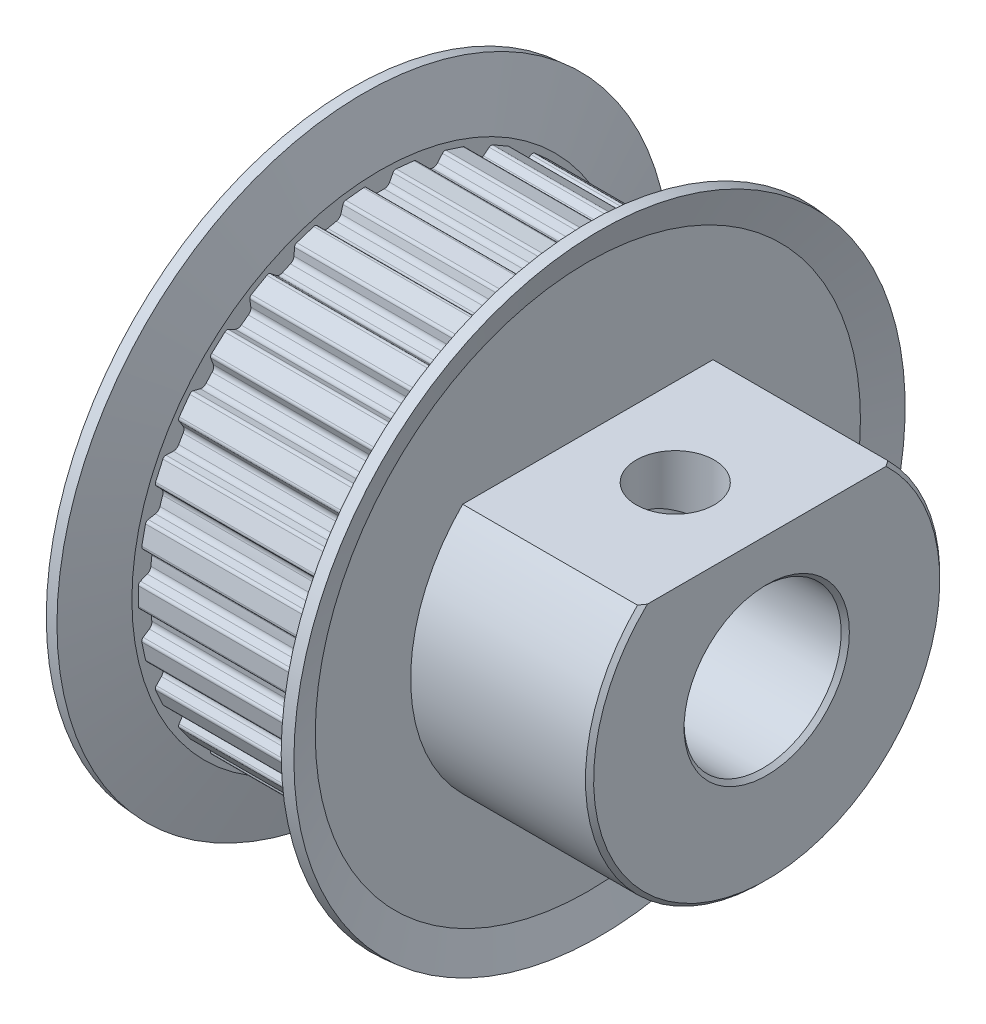
SolidWorks part; units mm, degrees
ref_plane "Front Plane" through (0, 0, 0) normal (0, 0, 1) x (1, 0, 0)
ref_plane "Top Plane" through (0, 0, 0) normal (0, 1, 0) x (1, 0, 0)
ref_plane "Right Plane" through (0, 0, 0) normal (1, 0, 0) x (0, 0, -1)
ref_plane "Plane1" through (0, 0, 0) normal (0, 0, -1) x (-1, 0, 0)
sketch "Sketch1" plane through (0, 0, 0) normal (0, 0, -1) x (-1, 0, 0)
  line L0 (-0.6794, 10.668) -> (-0.6794, 0)
  line L1 (-0.6794, 0) -> (8.0962, 0)
  line L2 (8.0962, 0) -> (8.0962, 10.668)
  line L3 (8.0962, 10.668) -> (8.5534, 11.9615)
  line L4 (8.5534, 11.9615) -> (8.0963, 12.0015)
  line L5 (8.0963, 12.0015) -> (7.4612, 9.7028)
  line L6 (7.4612, 9.7028) -> (7.4612, 8.9916)
  line L7 (7.4612, 8.9916) -> (0.0953, 8.9916)
  line L8 (0.0953, 8.9916) -> (0.0953, 9.7028)
  line L9 (0.0953, 9.7028) -> (-0.6794, 12.0015)
  line L10 (-0.6794, 12.0015) -> (-1.1366, 11.9615)
  line L11 (-1.1366, 11.9615) -> (-0.6794, 10.668)
  line L12 (-1.1366, 0) -> (8.5534, 0) construction
revolve "Revolve1" add sketch "Sketch1" angle 360 about L12 reverse direction yes
sketch "Sketch2" plane through (-8.0962, 0, 0) normal (-1, 0, 0) x (0, 0, 1)
  circle A0 centre (0, 0) radius 6.9342
extrude "Boss-Extrude1" add sketch "Sketch2" along normal blind 0.635
sketch "Sketch3" plane through (0.6794, 0, 0) normal (1, 0, 0) x (0, 0, -1)
  circle A0 centre (0, 0) radius 6.9342
extrude "Boss-Extrude2" add sketch "Sketch3" along normal blind 7
hole_wizard "Hole1" positions "Sketch5" profile "Sketch4" legacy
sketch "Sketch5" plane through (-8.7312, 0, 0) normal (-1, 0, 0) x (0, 0, 1)
  point P0 (0, 0)
sketch "Sketch4" plane through (-8.7312, 0, 0) normal (0, 1, 0) x (0, 0, 1)
  line L0 (0, 0) -> (0, 16.4107)
  line L1 (0, 16.4107) -> (3.075, 16.4107)
  line L2 (3.075, 16.4107) -> (3.075, 0)
  line L3 (3.075, 0) -> (0, 0)
  line L4 (0, 110) -> (0, -10) construction
  dimension "Diameter" = 6.15
  dimension "Depth" = 16.4107
sketch "Sketch8" plane through (0, 0, 0) normal (0, 1, 0) x (1, 0, 0)
  line L0 (-7.4612, -9.4488) -> (-0.0953, -9.4488)
rib "Rib1" sketch "Sketch8" sketch "Sketch8" thickness 0.8682 extrusion direction parallel to sketch draft on yes draft angle 22 parameters "D1"=0.8682, "D3"=22
ref_plane "Plane2" through (0, 0, 0) normal (0, -1, 0) x (1, 0, 0)
sketch "Sketch9" plane through (0, 0, 0) normal (0, -1, 0) x (1, 0, 0)
  line L0 (-7.4612, -9.4488) -> (-0.0953, -9.4488)
rib "Rib2" sketch "Sketch9" sketch "Sketch9" thickness 0.8682 extrusion direction parallel to sketch draft on yes draft angle 22 parameters "D1"=0.8682, "D3"=22
ref_plane "Plane3" through (0, 0, 0) normal (0, 0.1045, 0.9945) x (-1, 0, 0)
sketch "Sketch10" plane through (0, 0, 0) normal (0, 0.1045, 0.9945) x (-1, 0, 0)
  line L0 (7.4612, 9.4488) -> (0.0953, 9.4488)
rib "Rib3" sketch "Sketch10" sketch "Sketch10" thickness 0.8682 extrusion direction parallel to sketch draft on yes draft angle 22 parameters "D1"=0.8682, "D3"=22
ref_plane "Plane4" through (0, 0, 0) normal (0, -0.5, 0.866) x (1, 0, 0)
sketch "Sketch11" plane through (0, 0, 0) normal (0, -0.5, 0.866) x (1, 0, 0)
  line L0 (-7.4612, -9.4488) -> (-0.0953, -9.4488)
rib "Rib4" sketch "Sketch11" sketch "Sketch11" thickness 0.8682 extrusion direction parallel to sketch draft on yes draft angle 22 parameters "D1"=0.8682, "D3"=22
ref_plane "Plane5" through (0, 0, 0) normal (0, 0.9135, -0.4067) x (-1, 0, 0)
sketch "Sketch12" plane through (0, 0, 0) normal (0, 0.9135, -0.4067) x (-1, 0, 0)
  line L0 (7.4612, 9.4488) -> (0.0953, 9.4488)
rib "Rib5" sketch "Sketch12" sketch "Sketch12" thickness 0.8682 extrusion direction parallel to sketch draft on yes draft angle 22 parameters "D1"=0.8682, "D3"=22
ref_plane "Plane6" through (0, 0, 0) normal (0, -0.9135, 0.4067) x (1, 0, 0)
sketch "Sketch13" plane through (0, 0, 0) normal (0, -0.9135, 0.4067) x (1, 0, 0)
  line L0 (-7.4612, -9.4488) -> (-0.0953, -9.4488)
rib "Rib6" sketch "Sketch13" sketch "Sketch13" thickness 0.8682 extrusion direction parallel to sketch draft on yes draft angle 22 parameters "D1"=0.8682, "D3"=22
ref_plane "Plane7" through (0, 0, 0) normal (0, 0.809, 0.5878) x (-1, 0, 0)
sketch "Sketch14" plane through (0, 0, 0) normal (0, 0.809, 0.5878) x (-1, 0, 0)
  line L0 (7.4612, 9.4488) -> (0.0953, 9.4488)
rib "Rib7" sketch "Sketch14" sketch "Sketch14" thickness 0.8682 extrusion direction parallel to sketch draft on yes draft angle 22 parameters "D1"=0.8682, "D3"=22
ref_plane "Plane8" through (0, 0, 0) normal (0, -0.5, -0.866) x (1, 0, 0)
sketch "Sketch15" plane through (0, 0, 0) normal (0, -0.5, -0.866) x (1, 0, 0)
  line L0 (-7.4612, -9.4488) -> (-0.0953, -9.4488)
rib "Rib8" sketch "Sketch15" sketch "Sketch15" thickness 0.8682 extrusion direction parallel to sketch draft on yes draft angle 22 parameters "D1"=0.8682, "D3"=22
ref_plane "Plane9" through (0, 0, 0) normal (0, 0.5, -0.866) x (-1, 0, 0)
sketch "Sketch16" plane through (0, 0, 0) normal (0, 0.5, -0.866) x (-1, 0, 0)
  line L0 (7.4612, 9.4488) -> (0.0953, 9.4488)
rib "Rib9" sketch "Sketch16" sketch "Sketch16" thickness 0.8682 extrusion direction parallel to sketch draft on yes draft angle 22 parameters "D1"=0.8682, "D3"=22
ref_plane "Plane10" through (0, 0, 0) normal (0, -0.809, -0.5878) x (1, 0, 0)
sketch "Sketch17" plane through (0, 0, 0) normal (0, -0.809, -0.5878) x (1, 0, 0)
  line L0 (-7.4612, -9.4488) -> (-0.0953, -9.4488)
rib "Rib10" sketch "Sketch17" sketch "Sketch17" thickness 0.8682 extrusion direction parallel to sketch draft on yes draft angle 22 parameters "D1"=0.8682, "D3"=22
ref_plane "Plane11" through (0, 0, 0) normal (0, -0.9135, -0.4067) x (1, 0, 0)
sketch "Sketch18" plane through (0, 0, 0) normal (0, -0.9135, -0.4067) x (1, 0, 0)
  line L0 (-7.4612, -9.4488) -> (-0.0953, -9.4488)
rib "Rib11" sketch "Sketch18" sketch "Sketch18" thickness 0.8682 extrusion direction parallel to sketch draft on yes draft angle 22 parameters "D1"=0.8682, "D3"=22
ref_plane "Plane12" through (0, 0, 0) normal (0, -0.1045, -0.9945) x (1, 0, 0)
sketch "Sketch19" plane through (0, 0, 0) normal (0, -0.1045, -0.9945) x (1, 0, 0)
  line L0 (-7.4612, -9.4488) -> (-0.0953, -9.4488)
rib "Rib12" sketch "Sketch19" sketch "Sketch19" thickness 0.8682 extrusion direction parallel to sketch draft on yes draft angle 22 parameters "D1"=0.8682, "D3"=22
ref_plane "Plane13" through (0, 0, 0) normal (0, -0.9781, 0.2079) x (1, 0, 0)
sketch "Sketch20" plane through (0, 0, 0) normal (0, -0.9781, 0.2079) x (1, 0, 0)
  line L0 (-7.4612, -9.4488) -> (-0.0953, -9.4488)
rib "Rib13" sketch "Sketch20" sketch "Sketch20" thickness 0.8682 extrusion direction parallel to sketch draft on yes draft angle 22 parameters "D1"=0.8682, "D3"=22
ref_plane "Plane14" through (0, 0, 0) normal (0, 0.9135, 0.4067) x (-1, 0, 0)
sketch "Sketch21" plane through (0, 0, 0) normal (0, 0.9135, 0.4067) x (-1, 0, 0)
  line L0 (7.4612, 9.4488) -> (0.0953, 9.4488)
rib "Rib14" sketch "Sketch21" sketch "Sketch21" thickness 0.8682 extrusion direction parallel to sketch draft on yes draft angle 22 parameters "D1"=0.8682, "D3"=22
ref_plane "Plane15" through (0, 0, 0) normal (0, -0.309, -0.9511) x (1, 0, 0)
sketch "Sketch22" plane through (0, 0, 0) normal (0, -0.309, -0.9511) x (1, 0, 0)
  line L0 (-7.4612, -9.4488) -> (-0.0953, -9.4488)
rib "Rib15" sketch "Sketch22" sketch "Sketch22" thickness 0.8682 extrusion direction parallel to sketch draft on yes draft angle 22 parameters "D1"=0.8682, "D3"=22
ref_plane "Plane16" through (0, 0, 0) normal (0, -0.809, 0.5878) x (1, 0, 0)
sketch "Sketch23" plane through (0, 0, 0) normal (0, -0.809, 0.5878) x (1, 0, 0)
  line L0 (-7.4612, -9.4488) -> (-0.0953, -9.4488)
rib "Rib16" sketch "Sketch23" sketch "Sketch23" thickness 0.8682 extrusion direction parallel to sketch draft on yes draft angle 22 parameters "D1"=0.8682, "D3"=22
ref_plane "Plane17" through (0, 0, 0) normal (0, 0.9781, 0.2079) x (-1, 0, 0)
sketch "Sketch24" plane through (0, 0, 0) normal (0, 0.9781, 0.2079) x (-1, 0, 0)
  line L0 (7.4612, 9.4488) -> (0.0953, 9.4488)
rib "Rib17" sketch "Sketch24" sketch "Sketch24" thickness 0.8682 extrusion direction parallel to sketch draft on yes draft angle 22 parameters "D1"=0.8682, "D3"=22
ref_plane "Plane18" through (0, 0, 0) normal (0, -0.9781, -0.2079) x (1, 0, 0)
sketch "Sketch25" plane through (0, 0, 0) normal (0, -0.9781, -0.2079) x (1, 0, 0)
  line L0 (-7.4612, -9.4488) -> (-0.0953, -9.4488)
rib "Rib18" sketch "Sketch25" sketch "Sketch25" thickness 0.8682 extrusion direction parallel to sketch draft on yes draft angle 22 parameters "D1"=0.8682, "D3"=22
ref_plane "Plane19" through (0, 0, 0) normal (0, 0.5, 0.866) x (-1, 0, 0)
sketch "Sketch26" plane through (0, 0, 0) normal (0, 0.5, 0.866) x (-1, 0, 0)
  line L0 (7.4612, 9.4488) -> (0.0953, 9.4488)
rib "Rib19" sketch "Sketch26" sketch "Sketch26" thickness 0.8682 extrusion direction parallel to sketch draft on yes draft angle 22 parameters "D1"=0.8682, "D3"=22
ref_plane "Plane20" through (0, 0, 0) normal (0, -0.6691, 0.7431) x (1, 0, 0)
sketch "Sketch27" plane through (0, 0, 0) normal (0, -0.6691, 0.7431) x (1, 0, 0)
  line L0 (-7.4612, -9.4488) -> (-0.0953, -9.4488)
rib "Rib20" sketch "Sketch27" sketch "Sketch27" thickness 0.8682 extrusion direction parallel to sketch draft on yes draft angle 22 parameters "D1"=0.8682, "D3"=22
ref_plane "Plane21" through (0, 0, 0) normal (0, 0.9781, -0.2079) x (-1, 0, 0)
sketch "Sketch28" plane through (0, 0, 0) normal (0, 0.9781, -0.2079) x (-1, 0, 0)
  line L0 (7.4612, 9.4488) -> (0.0953, 9.4488)
rib "Rib21" sketch "Sketch28" sketch "Sketch28" thickness 0.8682 extrusion direction parallel to sketch draft on yes draft angle 22 parameters "D1"=0.8682, "D3"=22
ref_plane "Plane22" through (0, 0, 0) normal (0, 0.6691, -0.7431) x (-1, 0, 0)
sketch "Sketch29" plane through (0, 0, 0) normal (0, 0.6691, -0.7431) x (-1, 0, 0)
  line L0 (7.4612, 9.4488) -> (0.0953, 9.4488)
rib "Rib22" sketch "Sketch29" sketch "Sketch29" thickness 0.8682 extrusion direction parallel to sketch draft on yes draft angle 22 parameters "D1"=0.8682, "D3"=22
ref_plane "Plane23" through (0, 0, 0) normal (0, 0.6691, 0.7431) x (-1, 0, 0)
sketch "Sketch30" plane through (0, 0, 0) normal (0, 0.6691, 0.7431) x (-1, 0, 0)
  line L0 (7.4612, 9.4488) -> (0.0953, 9.4488)
rib "Rib23" sketch "Sketch30" sketch "Sketch30" thickness 0.8682 extrusion direction parallel to sketch draft on yes draft angle 22 parameters "D1"=0.8682, "D3"=22
ref_plane "Plane24" through (0, 0, 0) normal (0, -0.6691, -0.7431) x (1, 0, 0)
sketch "Sketch31" plane through (0, 0, 0) normal (0, -0.6691, -0.7431) x (1, 0, 0)
  line L0 (-7.4612, -9.4488) -> (-0.0953, -9.4488)
rib "Rib24" sketch "Sketch31" sketch "Sketch31" thickness 0.8682 extrusion direction parallel to sketch draft on yes draft angle 22 parameters "D1"=0.8682, "D3"=22
ref_plane "Plane25" through (0, 0, 0) normal (0, -0.309, 0.9511) x (1, 0, 0)
sketch "Sketch32" plane through (0, 0, 0) normal (0, -0.309, 0.9511) x (1, 0, 0)
  line L0 (-7.4612, -9.4488) -> (-0.0953, -9.4488)
rib "Rib25" sketch "Sketch32" sketch "Sketch32" thickness 0.8682 extrusion direction parallel to sketch draft on yes draft angle 22 parameters "D1"=0.8682, "D3"=22
ref_plane "Plane26" through (0, 0, 0) normal (0, 0.309, 0.9511) x (-1, 0, 0)
sketch "Sketch33" plane through (0, 0, 0) normal (0, 0.309, 0.9511) x (-1, 0, 0)
  line L0 (7.4612, 9.4488) -> (0.0953, 9.4488)
rib "Rib26" sketch "Sketch33" sketch "Sketch33" thickness 0.8682 extrusion direction parallel to sketch draft on yes draft angle 22 parameters "D1"=0.8682, "D3"=22
ref_plane "Plane27" through (0, 0, 0) normal (0, 0.309, -0.9511) x (-1, 0, 0)
sketch "Sketch34" plane through (0, 0, 0) normal (0, 0.309, -0.9511) x (-1, 0, 0)
  line L0 (7.4612, 9.4488) -> (0.0953, 9.4488)
rib "Rib27" sketch "Sketch34" sketch "Sketch34" thickness 0.8682 extrusion direction parallel to sketch draft on yes draft angle 22 parameters "D1"=0.8682, "D3"=22
ref_plane "Plane28" through (0, 0, 0) normal (0, 0.809, -0.5878) x (-1, 0, 0)
sketch "Sketch35" plane through (0, 0, 0) normal (0, 0.809, -0.5878) x (-1, 0, 0)
  line L0 (7.4612, 9.4488) -> (0.0953, 9.4488)
rib "Rib28" sketch "Sketch35" sketch "Sketch35" thickness 0.8682 extrusion direction parallel to sketch draft on yes draft angle 22 parameters "D1"=0.8682, "D3"=22
ref_plane "Plane29" through (0, 0, 0) normal (0, -0.1045, 0.9945) x (1, 0, 0)
sketch "Sketch36" plane through (0, 0, 0) normal (0, -0.1045, 0.9945) x (1, 0, 0)
  line L0 (-7.4612, -9.4488) -> (-0.0953, -9.4488)
rib "Rib29" sketch "Sketch36" sketch "Sketch36" thickness 0.8682 extrusion direction parallel to sketch draft on yes draft angle 22 parameters "D1"=0.8682, "D3"=22
sketch "Sketch37" plane through (0, 0, 0) normal (0, -0.1045, 0.9945) x (1, 0, 0)
  line L0 (-0.0953, 9.4488) -> (-7.4612, 9.4488)
rib "Rib30" sketch "Sketch37" sketch "Sketch37" thickness 0.8682 extrusion direction parallel to sketch draft on yes draft angle 22 parameters "D1"=0.8682, "D3"=22
chamfer "Chamfer2" distance 0.16 angle 45 3 edges at (7.6795, 0, 3.075) (7.6795, 0, -6.9342) (-8.7312, 0, 3.075)
fillet "Fillet1" radius 0.127 60 edges at (-3.7783, 4.2397, -8.4553) (-3.7783, -8.8522, -3.3327) (-3.7783, -3.4466, -8.8085) (-3.7783, -2.3891, 9.1521) (-3.7783, 5.2027, 7.8994) (-3.7783, -0.4341, 9.4488) (-3.7783, 0.4341, -9.4488) (-3.7783, 0.4341, 9.4488) (-3.7783, -6.7314, -6.6451) (-3.7783, 2.3891, 9.1521) (-3.7783, -9.4424, 0.556) (-3.7783, 4.2397, 8.4553) (-3.7783, 5.9051, -7.3891) (-3.7783, 5.9051, 7.3891) (-3.7783, 2.3891, -9.1521) (-3.7783, 7.3123, 5.9999) (-3.7783, -1.5399, -9.3326) (-3.7783, 8.3999, 4.3485) (-3.7783, -5.2027, -7.8994) (-3.7783, 8.8522, 3.3327) (-3.7783, -7.9659, -5.1003) (-3.7783, 9.1205, 2.507) (-3.7783, -9.3517, -1.4194) (-3.7783, 9.3517, 1.4194) (-3.7783, -9.1205, 2.507) (-3.7783, 1.5399, 9.3326) (-3.7783, -4.2397, 8.4553) (-3.7783, -1.5399, 9.3326) (-3.7783, 5.2027, -7.8994) (-3.7783, -3.4466, 8.8085) (-3.7783, 3.4466, -8.8085) (-3.7783, -5.2027, 7.8994) (-3.7783, 1.5399, -9.3326) (-3.7783, -6.7314, 6.6451) (-3.7783, -0.4341, -9.4488) (-3.7783, -7.9659, 5.1003) (-3.7783, -2.3891, -9.1521) (-3.7783, 9.4424, 0.556) (-3.7783, -4.2397, -8.4553) (-3.7783, 9.4424, -0.556) (-3.7783, -5.9051, -7.3891) (-3.7783, 7.9659, 5.1003) (-3.7783, -7.3123, -5.9999) (-3.7783, 6.7314, 6.6451) (-3.7783, -8.3999, -4.3485) (-3.7783, 9.3517, -1.4194) (-3.7783, -9.1205, -2.507) (-3.7783, 9.1205, -2.507) (-3.7783, -9.4424, -0.556) (-3.7783, 8.8522, -3.3327) (-3.7783, -9.3517, 1.4194) (-3.7783, 8.3999, -4.3485) (-3.7783, -8.8522, 3.3327) (-3.7783, 7.9659, -5.1003) (-3.7783, 3.4466, 8.8085) (-3.7783, 7.3123, -5.9999) (-3.7783, 6.7314, -6.6451) (-3.7783, -7.3123, 5.9999) (-3.7783, -5.9051, 7.3891) (-3.7783, -8.3999, 4.3485) tangent propagation no
fillet "Fillet2" radius 0.2286 60 edges at (-3.7783, -8.7246, -2.1748) (-3.7783, -1.2509, 8.9042) (-3.7783, -7.4541, 5.0284) (-3.7783, -7.4541, -5.0284) (-3.7783, 5.78, 6.8877) (-3.7783, -6.2458, -6.4683) (-3.7783, -8.8549, 1.5618) (-3.7783, -4.7644, -7.6256) (-3.7783, -4.7644, 7.6256) (-3.7783, -3.0749, -8.4495) (-3.7783, 2.4789, 8.6432) (-3.7783, -1.2509, -8.9042) (-3.7783, 8.0818, 3.9412) (-3.7783, 1.2509, -8.9042) (-3.7783, -8.9861, -0.3133) (-3.7783, 3.0749, -8.4495) (-3.7783, -8.3367, 3.3687) (-3.7783, 4.7644, -7.6256) (-3.7783, -6.2458, 6.4683) (-3.7783, 6.2458, -6.4683) (-3.7783, -3.0749, 8.4495) (-3.7783, 7.4541, -5.0284) (-3.7783, 0.6277, 8.9697) (-3.7783, 8.9861, 0.3133) (-3.7783, 4.2217, 7.9389) (-3.7783, 8.9861, -0.3133) (-3.7783, 7.0858, 5.5354) (-3.7783, 8.3367, 3.3687) (-3.7783, -8.3367, -3.3687) (-3.7783, 8.8549, 1.5618) (-3.7783, -8.8549, -1.5618) (-3.7783, 8.8549, -1.5618) (-3.7783, -8.9861, 0.3133) (-3.7783, 8.7246, -2.1748) (-3.7783, -8.7246, 2.1748) (-3.7783, 8.3367, -3.3687) (-3.7783, -8.0818, 3.9412) (-3.7783, 8.0818, -3.9412) (-3.7783, -7.0858, 5.5354) (-3.7783, 7.0858, -5.5354) (-3.7783, -5.78, 6.8877) (-3.7783, 5.78, -6.8877) (-3.7783, -4.2217, 7.9389) (-3.7783, 4.2217, -7.9389) (-3.7783, -2.4789, 8.6432) (-3.7783, 2.4789, -8.6432) (-3.7783, -0.6277, 8.9697) (-3.7783, 0.6277, -8.9697) (-3.7783, 1.2509, 8.9042) (-3.7783, -0.6277, -8.9697) (-3.7783, 3.0749, 8.4495) (-3.7783, -2.4789, -8.6432) (-3.7783, 4.7644, 7.6256) (-3.7783, -4.2217, -7.9389) (-3.7783, 6.2458, 6.4683) (-3.7783, -5.78, -6.8877) (-3.7783, 7.4541, 5.0284) (-3.7783, -7.0858, -5.5354) (-3.7783, -8.0818, -3.9412) (-3.7783, 8.7246, 2.1748) tangent propagation no
sketch "Sketch38" plane through (7.6795, 0, 0) normal (1, 0, 0) x (0, 0, -1)
  line L0 (-4.8987, 4.9078) -> (4.8987, 4.9078)
  line L1 (-4.8987, 4.9078) -> (-4.8987, 7.2729)
  line L2 (4.8987, 4.9078) -> (4.8987, 7.2729)
  line L3 (-4.8987, 7.2729) -> (4.8987, 7.2729)
  circle A0 centre (0, 0) radius 6.9342 construction
  circle A1 centre (0, 0) radius 6.9342 construction
  point P8 (-4.8987, 4.9078)
  point P9 (0, 0)
extrude "Cut-Extrude1" cut sketch "Sketch38" against normal blind 7
sketch "Sketch39" plane through (0, 4.9078, 0) normal (0, 1, 0) x (1, 0, 0)
  line L0 (4.0994, -4.8987) -> (4.0994, 4.8987) construction
  line L1 (0.6794, -4.8987) -> (7.5194, -4.8987) construction
  line L2 (0.6794, 4.8987) -> (7.5194, 4.8987) construction
  line L3 (7.6795, -4.6694) -> (7.6795, 4.6694) construction
  line L4 (7.6795, 0) -> (4.0994, 0) construction
  circle A0 centre (4.0994, 0) radius 1.525
  dimension "D1" = 3.05
extrude "Cut-Extrude2" cut sketch "Sketch39" against normal blind 4.57
